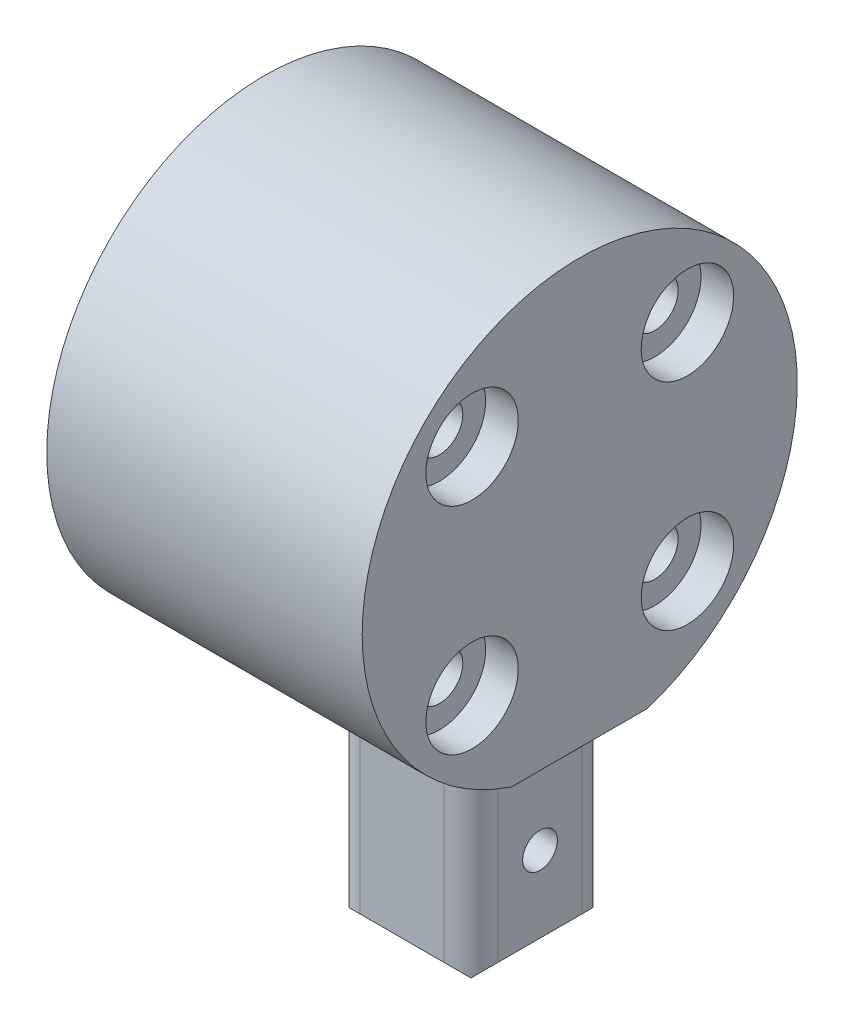
SolidWorks part; units mm, degrees
ref_plane "前视基准面" through (0, 0, 0) normal (0, 0, 1) x (1, 0, 0)
ref_plane "上视基准面" through (0, 0, 0) normal (0, 1, 0) x (1, 0, 0)
ref_plane "右视基准面" through (0, 0, 0) normal (1, 0, 0) x (0, 0, -1)
sketch "草图1" plane through (0, 0, 0) normal (1, 0, 0) x (0, 0, -1)
  circle A0 centre (0, 0) radius 20
  dimension "D1" = 40
extrude "凸台-拉伸1" add sketch "草图1" along normal blind 10
sketch "草图2" plane through (0, 0, 0) normal (-1, 0, 0) x (0, 0, 1)
  line L1 (-7.5, -15.25) -> (7.5, -15.25)
  line L2 (-7.5, -15.25) -> (-7.5, 15.25)
  line L3 (-7.5, 15.25) -> (7.5, 15.25)
  line L4 (7.5, -15.25) -> (7.5, 15.25)
  line L5 (-7.5, -15.25) -> (7.5, 15.25) construction
  line L6 (-7.5, 15.25) -> (7.5, -15.25) construction
  point P0 (0, 0)
  dimension "D1" = 15
  dimension "D2" = 30.5
extrude "切除-拉伸1" cut sketch "草图2" against normal blind 4
sketch "草图3" plane through (4, 0, 0) normal (-1, 0, 0) x (0, 0, 1)
  circle A0 centre (0, 0) radius 8.75
  dimension "D1" = 17.5
extrude "切除-拉伸2" cut sketch "草图3" along normal blind 4
sketch "草图4" plane through (0, 0, 0) normal (-1, 0, 0) x (0, 0, 1)
  line L1 (-9, -16) -> (9, -16)
  line L2 (-9, -16) -> (-9, 16)
  line L3 (-9, 16) -> (9, 16)
  line L4 (9, -16) -> (9, 16)
  line L5 (-9, -16) -> (9, 16) construction
  line L6 (-9, 16) -> (9, -16) construction
  circle A0 centre (0, 0) radius 20
  dimension "D3" = 40
  dimension "D1" = 32
  dimension "D2" = 18
extrude "凸台-拉伸2" add sketch "草图4" along normal blind 19
fillet "圆角1" radius 3 4 edges at (-9.5, -16, -9) (-9.5, -16, 9) (-9.5, 16, -9) (-9.5, 16, 9)
sketch "草图5" plane through (-19, 0, 0) normal (-1, 0, 0) x (0, 0, 1)
  line L0 (-6, -16) -> (6, -16) construction
  line L1 (6, 16) -> (-6, 16) construction
  circle A0 centre (0, -16) radius 2.5
  circle A1 centre (0, 16) radius 2.5
  dimension "D1" = 5
  dimension "D2" = 5
extrude "切除-拉伸3" cut sketch "草图5" against normal blind 20
fillet "圆角2" radius 3 4 edges at (-9.5, -16, -2.5) (-9.5, -16, 2.5) (-9.5, 16, -2.5) (-9.5, 16, 2.5)
sketch "草图6" plane through (10, 0, 0) normal (1, 0, 0) x (0, 0, -1)
  line L0 (0, 0) -> (20, 0) construction
  line L1 (0, 0) -> (18.216, -18.216) construction
  circle A0 centre (0, 0) radius 14 construction
  circle A2 centre (9.8995, -9.8995) radius 2.15
  circle A3 centre (0, 0) radius 14 construction
  circle A4 centre (-9.8995, -9.8995) radius 2.15
  circle A5 centre (0, 0) radius 14 construction
  circle A6 centre (-9.8995, 9.8995) radius 2.15
  circle A7 centre (0, 0) radius 14 construction
  circle A8 centre (9.8995, 9.8995) radius 2.15
  point P21 (0, 0)
  dimension "D1" = 28
  dimension "D3" = 4.3
  dimension "D2" = 45
  dimension "D4" = 4
extrude "切除-拉伸4" cut sketch "草图6" against normal blind 43
fillet "圆角3" radius 1 8 edges at (-9.5, -11.8523, 9) (-9.5, -7.9467, 9) (-9.5, -11.8523, -9) (-9.5, -7.9467, -9) (-9.5, 7.9467, -9) (-9.5, 11.8523, -9) (-9.5, 7.9467, 9) (-9.5, 11.8523, 9)
sketch "草图7" plane through (10, 0, 0) normal (1, 0, 0) x (0, 0, -1)
  circle A0 centre (9.8995, -9.8995) radius 4.25
  dimension "D1" = 8.5
extrude "切除-拉伸5" cut sketch "草图7" against normal blind 3
pattern_circular "阵列(圆周)1" count 4 over 360 about axis through (10, 0, 0) along (1, 0, 0) of "切除-拉伸5"
sketch "草图8" plane through (10, 0, 0) normal (1, 0, 0) x (0, 0, -1)
  line L1 (-11.4701, -19) -> (11.4701, -19)
  line L2 (-11.4701, -19) -> (-11.4701, -28.3124)
  line L3 (-11.4701, -28.3124) -> (11.4701, -28.3124)
  line L4 (11.4701, -19) -> (11.4701, -28.3124)
  line L5 (-11.4701, -19) -> (11.4701, -28.3124) construction
  line L6 (-11.4701, -28.3124) -> (11.4701, -19) construction
  point P0 (0, -23.6562)
  dimension "D1" = 19
extrude "切除-拉伸6" cut sketch "草图8" against normal blind 20
sketch "草图9" plane through (0, -19, 0) normal (0, -1, 0) x (1, 0, 0)
  line L1 (-3, -3) -> (3, -3)
  line L2 (-3, -3) -> (-3, 3)
  line L3 (-3, 3) -> (3, 3)
  line L4 (3, -3) -> (3, 3)
  line L5 (-3, -3) -> (3, 3) construction
  line L6 (-3, 3) -> (3, -3) construction
  point P0 (0, 0)
  dimension "D1" = 6
  dimension "D2" = 6
extrude "切除-拉伸7" cut sketch "草图9" against normal blind 4
sketch "草图10" plane through (0, -19, 0) normal (0, -1, 0) x (1, 0, 0)
  line L0 (10, -6.245) -> (10, 6.245) construction
  line L1 (-6.35, -6.35) -> (6.35, -6.35)
  line L2 (-6.35, -6.35) -> (-6.35, 6.35)
  line L3 (-6.35, 6.35) -> (6.35, 6.35)
  line L4 (6.35, -6.35) -> (6.35, 6.35)
  line L5 (-6.35, -6.35) -> (6.35, 6.35) construction
  line L6 (-6.35, 6.35) -> (6.35, -6.35) construction
  line L7 (-3, -3) -> (3, -3)
  line L8 (-3, -3) -> (-3, 3)
  line L9 (-3, 3) -> (3, 3)
  line L10 (3, -3) -> (3, 3)
  line L11 (-3, -3) -> (3, 3) construction
  line L12 (-3, 3) -> (3, -3) construction
  point P0 (0, 0)
  point P6 (0, 0)
  dimension "D1" = 12.7
  dimension "D2" = 12.7
  dimension "D3" = 10
extrude "凸台-拉伸3" add sketch "草图10" along normal blind 20 and the other way blind 0.5
sketch "草图11" plane through (-6.35, 0, 0) normal (-1, 0, 0) x (0, 0, 1)
  line L0 (-6.245, -19) -> (6.245, -19) construction
  line L1 (6.35, -18.9652) -> (6.35, -39) construction
  line L2 (-6.35, -18.9652) -> (-6.35, -39) construction
  circle A0 centre (0, -29) radius 1.6
  dimension "D1" = 3.2
  dimension "D2" = 10
  dimension "D3" = 6.35
  dimension "D4" = 6.35
extrude "切除-拉伸8" cut sketch "草图11" against normal blind 20
chamfer "倒角1" distance 3 angle 45 2 edges at (-3, -27.7342, -3) (-3, -27.7342, 3)
fillet "圆角4" radius 2 4 edges at (-0.5003, -16.8675, 2.4997) (-0.5003, -16.8675, -2.4997) (-1.8082, -18.1976, 1.1918) (-1.8082, -18.1976, -1.1918)
chamfer "倒角2" distance 3 angle 45 4 edges at (6.35, -39, 0) (0, -39, -6.35) (-6.35, -39, 0) (0, -39, 6.35)
sketch "草图13" plane through (0, -39, 0) normal (0, -1, 0) x (1, 0, 0)
  circle A0 centre (0, 0) radius 3.35
  dimension "D1" = 6.7
fillet "圆角5" radius 2.5 4 edges at (6.35, -27.4826, -6.35) (6.35, -27.4826, 6.35) (-6.35, -27.4826, 6.35) (-6.35, -27.4826, -6.35)
